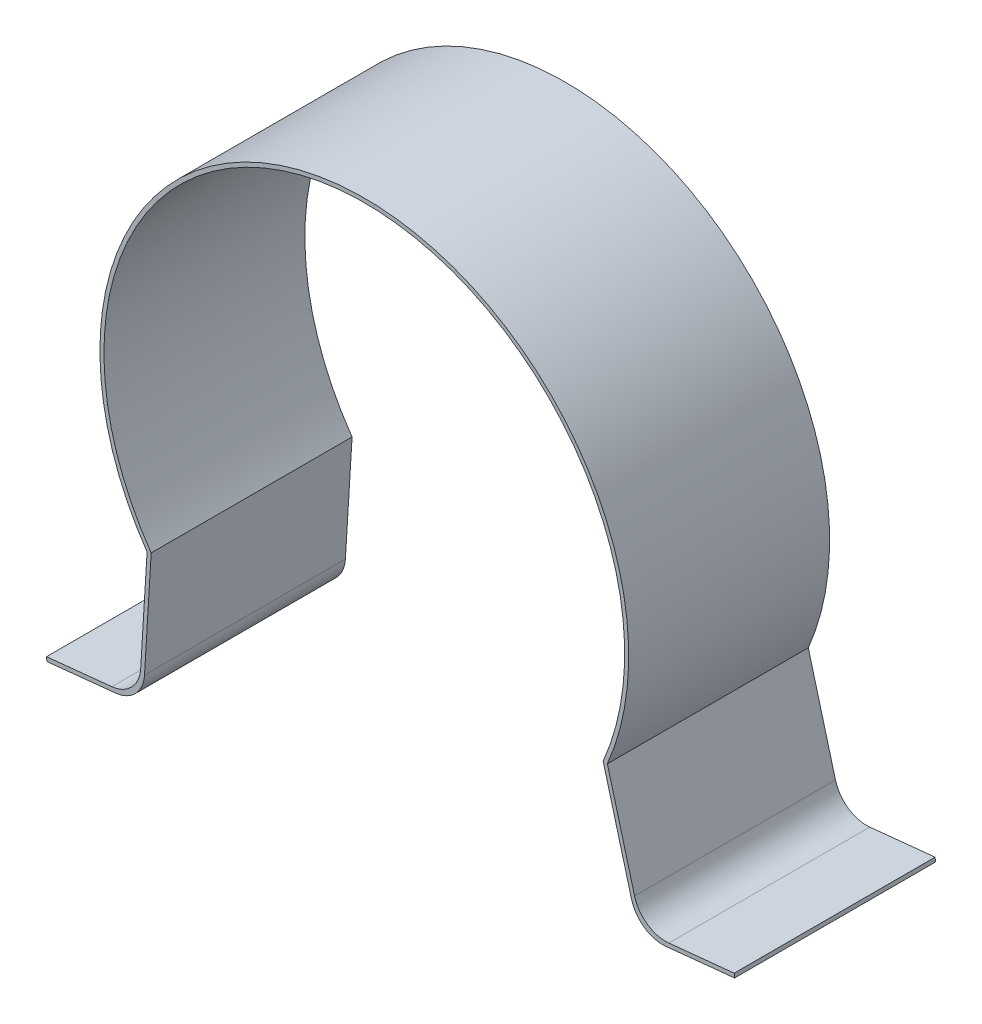
SolidWorks part; units mm, degrees
ref_plane "Спереди" through (0, 0, 0) normal (0, 0, 1) x (1, 0, 0)
ref_plane "Сверху" through (0, 0, 0) normal (0, 1, 0) x (1, 0, 0)
ref_plane "Справа" through (0, 0, 0) normal (1, 0, 0) x (0, 0, -1)
sketch "Эскиз8" plane through (0, 0, 0) normal (0, 0, 1) x (1, 0, 0)
  line L0 (-26.5227, -18.6093) -> (-27.5606, -35.5776)
  line L1 (-27.5606, -35.5776) -> (-39.4981, -36.8007)
  line L2 (0, 31.1118) -> (0, 49.2071) construction
  line L3 (34.1389, -29.3254) -> (46.0777, -28.1156)
  line L4 (29.7166, -12.9106) -> (34.1389, -29.3254)
  line L6 (46.0777, -28.1156) -> (-39.4841, -36.7858) construction
  arc A0 (29.7166, -12.9106) -> (-26.5227, -18.6093) centre (0, 0) ccw
  arc A1 (10.0641, 30.7973) -> (-18.6079, -26.5237) centre (0, 0) ccw construction
extrude "Вытянуть-Тонкостенный1" add sketch "Эскиз8" along normal blind 25 thin thin type one direction reverse wall 0.5
fillet "Скругление1" radius 4 1 edges at (-28.0338, -35.1234, 12.5)
fillet "Скругление2" radius 4 1 edges at (-27.5606, -35.5776, 12.5)
fillet "Скругление3" radius 4 2 edges at (34.1389, -29.3254, 12.5) (34.5111, -28.7851, 12.5)
